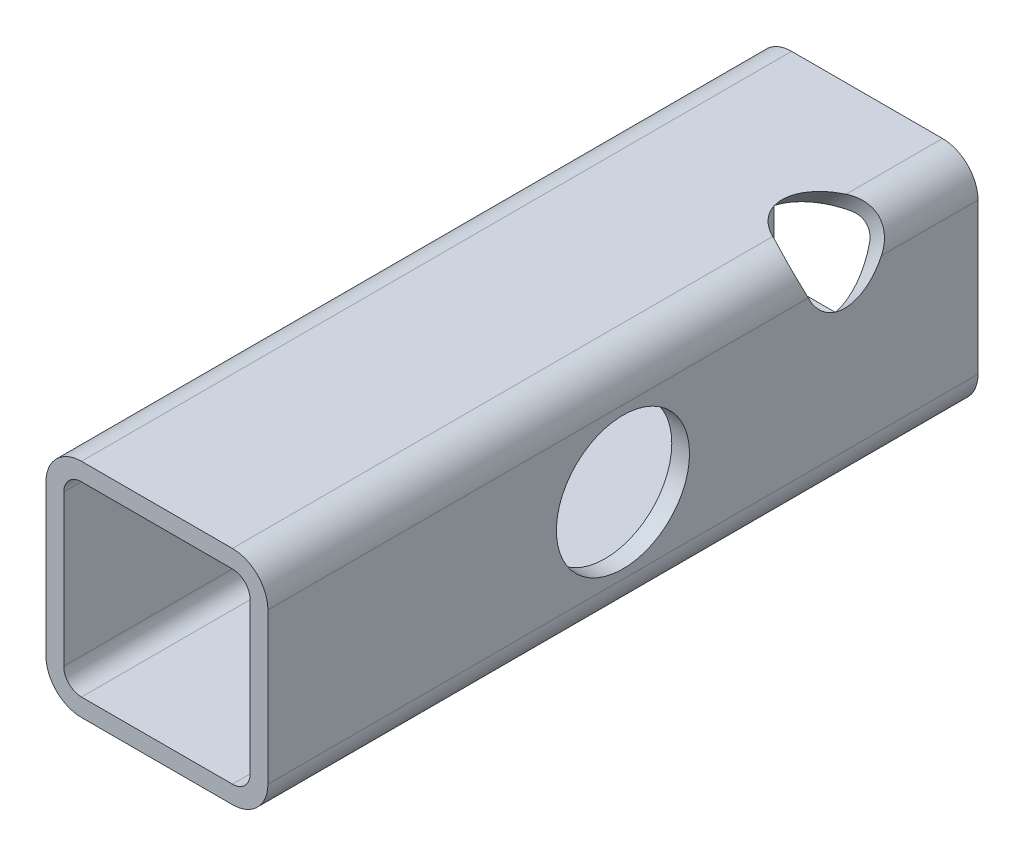
SolidWorks part; units mm, degrees
material "1060 Сплав"
ref_plane "Front" through (0, 0, 0) normal (0, 0, 1) x (1, 0, 0)
ref_plane "Top" through (0, 0, 0) normal (0, 1, 0) x (1, 0, 0)
ref_plane "Right" through (0, 0, 0) normal (1, 0, 0) x (0, 0, -1)
sketch "Эскиз1" plane through (0, 0, 0) normal (0, 0, 1) x (1, 0, 0)
  line L0 (-10.5, -8.5) -> (-10.5, 8.5)
  line L1 (8.5, -12.5) -> (-8.5, -12.5)
  line L2 (12.5, -8.5) -> (12.5, 8.5)
  line L3 (8.5, 12.5) -> (-8.5, 12.5)
  line L4 (-12.5, -8.5) -> (-12.5, 8.5)
  line L5 (12.5, -12.5) -> (-12.5, 12.5) construction
  line L6 (12.5, 12.5) -> (-12.5, -12.5) construction
  line L7 (8.5, 10.5) -> (-8.5, 10.5)
  line L8 (10.5, -8.5) -> (10.5, 8.5)
  line L9 (8.5, -10.5) -> (-8.5, -10.5)
  arc A0 (-12.5, -8.5) -> (-8.5, -12.5) centre (-8.5, -8.5) ccw
  arc A1 (8.5, -12.5) -> (12.5, -8.5) centre (8.5, -8.5) ccw
  arc A2 (12.5, 8.5) -> (8.5, 12.5) centre (8.5, 8.5) ccw
  arc A3 (-12.5, 8.5) -> (-8.5, 12.5) centre (-8.5, 8.5) cw
  arc A4 (-10.5, 8.5) -> (-8.5, 10.5) centre (-8.5, 8.5) cw
  arc A5 (10.5, 8.5) -> (8.5, 10.5) centre (8.5, 8.5) ccw
  arc A6 (8.5, -10.5) -> (10.5, -8.5) centre (8.5, -8.5) ccw
  arc A7 (-10.5, -8.5) -> (-8.5, -10.5) centre (-8.5, -8.5) ccw
  point P0 (0, 0)
  dimension "D3" = 4
  dimension "D1" = 25
  dimension "D2" = 25
  dimension "D4" = 2
extrude "Бобышка-Вытянуть1" add sketch "Эскиз1" along normal blind 80
sketch "Эскиз2" plane through (12.5, 0, 0) normal (1, 0, 0) x (0, 0, -1)
  line L0 (-80, -8.5) -> (-80, 8.5) construction
  circle A0 centre (-40, 0) radius 7.5
  dimension "D1" = 15
  dimension "D2" = 40
extrude "Вырез-Вытянуть1" cut sketch "Эскиз2" against normal blind 3
sketch "Эскиз3" plane through (-12.5, 0, 0) normal (-1, 0, 0) x (0, 0, 1)
  line L0 (80, 8.5) -> (80, -8.5) construction
  circle A0 centre (40, 0) radius 4.25
  dimension "D1" = 8.5
  dimension "D2" = 40
extrude "Вырез-Вытянуть2" cut sketch "Эскиз3" against normal blind 3
ref_axis "Ось1" through (0, 0, 50) along (0, 0, -1)
ref_plane "Плоскость1" through (0, 0, 0) normal (0.7071, 0.7071, 0) x (0, 0, -1)
sketch "Эскиз4" plane through (0, 0, 0) normal (0.7071, 0.7071, 0) x (0, 0, -1)
  line L0 (0, -2.8284) -> (0, 2.8284) construction
  circle A0 centre (-15, 0) radius 5
  dimension "D1" = 15
  dimension "D2" = 10
extrude "Вырез-Вытянуть3" cut sketch "Эскиз4" along normal blind 20
